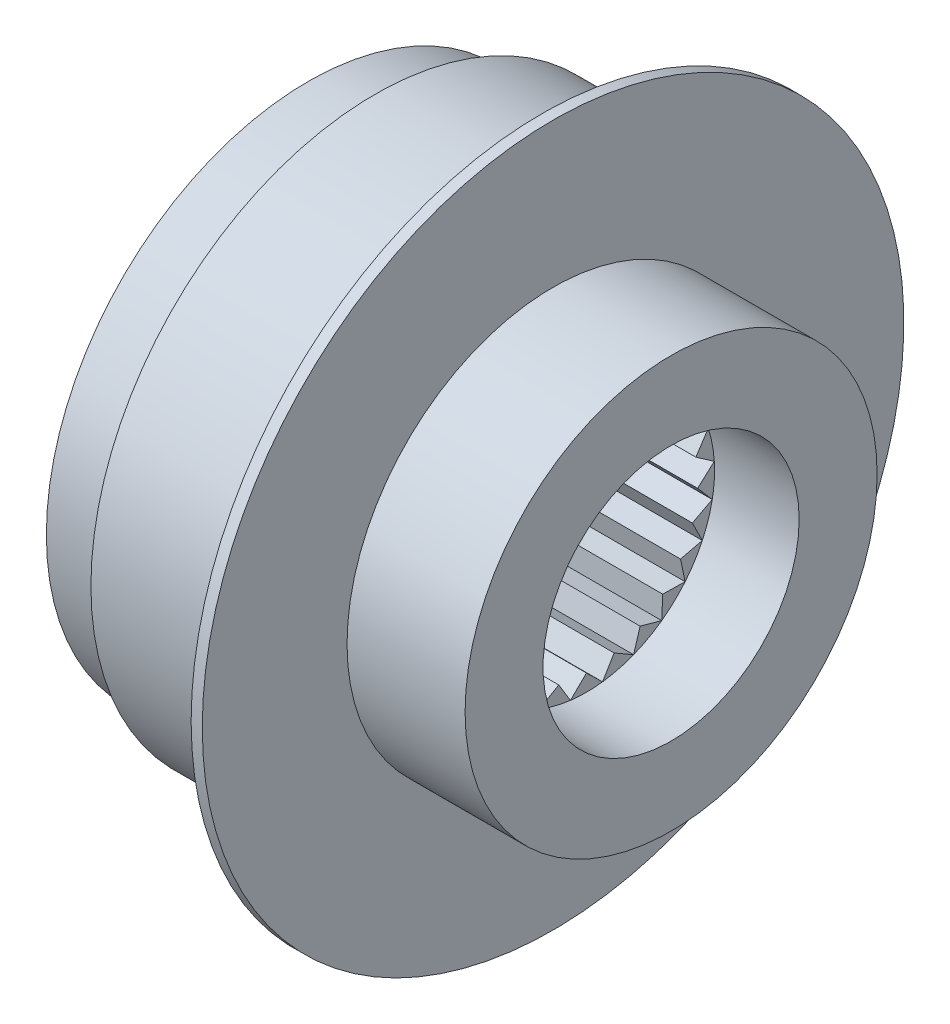
SolidWorks part; units mm, degrees
material "AISI 4130 Steel, normalized at 870C"
ref_plane "X-Y Datum" through (0, 0, 0) normal (0, 0, 1) x (1, 0, 0)
ref_plane "X-Z Datum" through (0, 0, 0) normal (0, 1, 0) x (1, 0, 0)
ref_plane "Y-Z Datum" through (0, 0, 0) normal (1, 0, 0) x (0, 0, -1)
sketch "Sketch1" plane through (0, 0, 0) normal (0, 1, 0) x (1, 0, 0)
  line L0 (-34.0129, 0) -> (34.0129, 0) construction
  line L11 (-20.701, -12.7) -> (-20.701, -29.845)
  line L12 (-20.701, -29.845) -> (-13.081, -29.845)
  line L13 (-13.081, -29.845) -> (-13.081, -32.385)
  line L14 (-13.081, -32.385) -> (5.969, -32.385)
  line L15 (5.969, -32.385) -> (5.969, -40.005)
  line L16 (5.969, -40.005) -> (7.239, -40.005)
  line L17 (7.239, -40.005) -> (7.239, -23.495)
  line L18 (7.239, -23.495) -> (20.701, -23.495)
  line L19 (20.701, -23.495) -> (20.701, -12.7)
  line L20 (20.701, -12.7) -> (-20.701, -12.7)
  point P4 (0, -12.7)
  dimension "D1" = 41.402
  dimension "D2" = 16.51
  dimension "D3" = 1.27
  dimension "D4" = 2.54
  dimension "D5" = 20.32
  dimension "D6" = 7.62
  dimension "D7" = 12.7
  dimension "D8" = 10.795
  dimension "D9" = 7.62
revolve "Revolve1" add sketch "Sketch1" angle 360 about L0
sketch "Sketch2" plane through (-20.701, 0, 0) normal (1, 0, 0) x (0, 0, -1)
  line L0 (0, 0) -> (22.225, 0) construction
  line L1 (0, 0) -> (-11.1125, -19.2474) construction
  circle A0 centre (0, 0) radius 22.225 construction
  circle A1 centre (22.225, 0) radius 3.9688
  circle A2 centre (-11.1125, -19.2474) radius 3.9687
  circle A3 centre (-11.1125, 19.2474) radius 3.9688
  dimension "D1" = 44.45
  dimension "D2" = 7.9375
  dimension "D4" = 120
  dimension "D5" = 22.225
  dimension "D3" = 3
extrude "Cut-Extrude1" cut sketch "Sketch2" along normal blind 6.35
sketch "Sketch3" plane through (20.701, 0, 0) normal (1, 0, 0) x (0, 0, -1)
  line L0 (0, 0) -> (0, -12.7) construction
  line L1 (0, 0) -> (1.5917, -12.5999) construction
  line L2 (0, 0) -> (3.1584, -12.301) construction
  line L3 (3.1584, -12.301) -> (1.8305, -14.4898)
  line L4 (1.8305, -14.4898) -> (0, -12.7)
  line L5 (-1.8305, -14.4898) -> (-3.1584, -12.301)
  line L6 (0, -12.7) -> (-1.8305, -14.4898)
  line L7 (-5.3765, -13.5794) -> (-6.1183, -11.1291)
  line L8 (-3.1584, -12.301) -> (-5.3765, -13.5794)
  line L9 (-8.5846, -11.8157) -> (-8.6937, -9.2579)
  line L10 (-6.1183, -11.1291) -> (-8.5846, -11.8157)
  line L11 (-11.2533, -9.3096) -> (-10.723, -6.805)
  line L12 (-8.6937, -9.2579) -> (-11.2533, -9.3096)
  line L13 (-13.215, -6.2185) -> (-12.0784, -3.9245)
  line L14 (-10.723, -6.805) -> (-13.215, -6.2185)
  line L15 (-14.3463, -2.7367) -> (-12.6749, -0.7974)
  line L16 (-12.0784, -3.9245) -> (-14.3463, -2.7367)
  line L17 (-14.5762, 0.9171) -> (-12.475, 2.3797)
  line L18 (-12.6749, -0.7974) -> (-14.5762, 0.9171)
  line L19 (-13.8902, 4.5132) -> (-11.4913, 5.4074)
  line L20 (-12.475, 2.3797) -> (-13.8902, 4.5132)
  line L21 (-12.3314, 7.8258) -> (-9.7855, 8.0953)
  line L22 (-11.4913, 5.4074) -> (-12.3314, 7.8258)
  line L23 (-9.9978, 10.6466) -> (-7.4649, 10.2745)
  line L24 (-9.7855, 8.0953) -> (-9.9978, 10.6466)
  line L25 (-7.036, 12.7985) -> (-4.6752, 11.8082)
  line L26 (-7.4649, 10.2745) -> (-7.036, 12.7985)
  line L27 (-3.6321, 14.1462) -> (-1.5917, 12.5999)
  line L28 (-4.6752, 11.8082) -> (-3.6321, 14.1462)
  line L29 (0, 14.605) -> (1.5917, 12.5999)
  line L30 (-1.5917, 12.5999) -> (0, 14.605)
  line L31 (3.6321, 14.1462) -> (4.6752, 11.8082)
  line L32 (1.5917, 12.5999) -> (3.6321, 14.1462)
  line L33 (7.036, 12.7985) -> (7.4649, 10.2745)
  line L34 (4.6752, 11.8082) -> (7.036, 12.7985)
  line L35 (9.9978, 10.6466) -> (9.7855, 8.0953)
  line L36 (7.4649, 10.2745) -> (9.9978, 10.6466)
  line L37 (12.3314, 7.8258) -> (11.4913, 5.4074)
  line L38 (9.7855, 8.0953) -> (12.3314, 7.8258)
  line L39 (13.8902, 4.5132) -> (12.475, 2.3797)
  line L40 (11.4913, 5.4074) -> (13.8902, 4.5132)
  line L41 (14.5762, 0.9171) -> (12.6749, -0.7974)
  line L42 (12.475, 2.3797) -> (14.5762, 0.9171)
  line L43 (14.3463, -2.7367) -> (12.0784, -3.9245)
  line L44 (12.6749, -0.7974) -> (14.3463, -2.7367)
  line L45 (13.215, -6.2185) -> (10.723, -6.805)
  line L46 (12.0784, -3.9245) -> (13.215, -6.2185)
  line L47 (11.2533, -9.3096) -> (8.6937, -9.2579)
  line L48 (10.723, -6.805) -> (11.2533, -9.3096)
  line L49 (8.5846, -11.8157) -> (6.1183, -11.1291)
  line L50 (8.6937, -9.2579) -> (8.5846, -11.8157)
  line L51 (5.3765, -13.5794) -> (3.1584, -12.301)
  line L52 (6.1183, -11.1291) -> (5.3765, -13.5794)
  circle A0 centre (0, 0) radius 12.7 construction
  circle A1 centre (0, 0) radius 14.605
  arc A2 (0, -12.7) -> (3.1584, -12.301) centre (0, 0) ccw
  arc A3 (-3.1584, -12.301) -> (0, -12.7) centre (0, 0) ccw
  arc A4 (-6.1183, -11.1291) -> (-3.1584, -12.301) centre (0, 0) ccw
  arc A5 (-8.6937, -9.2579) -> (-6.1183, -11.1291) centre (0, 0) ccw
  arc A6 (-10.723, -6.805) -> (-8.6937, -9.2579) centre (0, 0) ccw
  arc A7 (-12.0784, -3.9245) -> (-10.723, -6.805) centre (0, 0) ccw
  arc A8 (-12.6749, -0.7974) -> (-12.0784, -3.9245) centre (0, 0) ccw
  arc A9 (-12.475, 2.3797) -> (-12.6749, -0.7974) centre (0, 0) ccw
  arc A10 (-11.4913, 5.4074) -> (-12.475, 2.3797) centre (0, 0) ccw
  arc A11 (-9.7855, 8.0953) -> (-11.4913, 5.4074) centre (0, 0) ccw
  arc A12 (-7.4649, 10.2745) -> (-9.7855, 8.0953) centre (0, 0) ccw
  arc A13 (-4.6752, 11.8082) -> (-7.4649, 10.2745) centre (0, 0) ccw
  arc A14 (-1.5917, 12.5999) -> (-4.6752, 11.8082) centre (0, 0) ccw
  arc A15 (1.5917, 12.5999) -> (-1.5917, 12.5999) centre (0, 0) ccw
  arc A16 (4.6752, 11.8082) -> (1.5917, 12.5999) centre (0, 0) ccw
  arc A17 (7.4649, 10.2745) -> (4.6752, 11.8082) centre (0, 0) ccw
  arc A18 (9.7855, 8.0953) -> (7.4649, 10.2745) centre (0, 0) ccw
  arc A19 (11.4913, 5.4074) -> (9.7855, 8.0953) centre (0, 0) ccw
  arc A20 (12.475, 2.3797) -> (11.4913, 5.4074) centre (0, 0) ccw
  arc A21 (12.6749, -0.7974) -> (12.475, 2.3797) centre (0, 0) ccw
  arc A22 (12.0784, -3.9245) -> (12.6749, -0.7974) centre (0, 0) ccw
  arc A23 (10.723, -6.805) -> (12.0784, -3.9245) centre (0, 0) ccw
  arc A24 (8.6937, -9.2579) -> (10.723, -6.805) centre (0, 0) ccw
  arc A25 (6.1183, -11.1291) -> (8.6937, -9.2579) centre (0, 0) ccw
  arc A26 (3.1584, -12.301) -> (6.1183, -11.1291) centre (0, 0) ccw
  circle M5 centre (0, 0) radius 12.7
  dimension "D1" = 1.905
  dimension "D4" = 25
  dimension "D2" = 7.2
  dimension "D3" = 14.4
extrude "Cut-Extrude2" cut sketch "Sketch3" along normal blind 31.75 from surface contours L14 L13 M5 | L16 L15 M5 | L18 L17 M5 | L20 L19 M5 | L22 L21 M5 | L24 L23 M5 | L26 L25 M5 | L28 L27 M5 | L30 L29 M5 | L32 L31 M5 | L34 L33 M5 | L36 L35 M5 | L38 L37 M5 | L40 L39 M5 | L42 L41 M5 | L44 L43 M5 | L46 L45 M5 | L48 L47 M5 | L50 L49 M5 | L4 L3 M5 | L6 L5 M5 | L8 L7 M5 | L10 L9 M5 | L12 L11 M5 | L52 L51 A26 region at (20.701, -13.2081, -1.6686) region at (20.701, -13.2081, 1.6686) region at (20.701, -10.7705, -7.8252) region at (20.701, -12.3782, 4.9009) region at (20.701, -8.4861, -10.2579) region at (20.701, -10.7705, 7.8252) region at (20.701, -5.6684, -12.0461) region at (20.701, -8.4861, 10.2579) region at (20.701, -2.4946, -13.0773) region at (20.701, -5.6684, 12.0461) region at (20.701, 0.8359, -13.2868) region at (20.701, -2.4946, 13.0773) region at (20.701, 0.8359, 13.2868) region at (20.701, 4.114, -12.6615) region at (20.701, 4.114, 12.6615) region at (20.701, 7.1335, -11.2406) region at (20.701, 7.1335, 11.2406) region at (20.701, 9.7048, -9.1134) region at (20.701, 9.7048, 9.1134) region at (20.701, 11.6664, -6.4136) region at (20.701, 11.6664, 6.4136) region at (20.701, 12.8948, -3.3108) region at (20.701, 12.8948, 3.3108) region at (20.701, 13.3131, 0) starting at face at (-20.701, 0, -26.1937)
extrude "Cut-Extrude3" cut sketch "Sketch3<4>" against normal up to surface (9.652 mm away) contours L50 A1 L47 | M5 | L50 L49 M5 | L52 A1 L49 | L52 L51 M5 | L3 A1 L51 | L4 L3 M5 | L6 A1 L4 | L12 A1 L9 | L14 A1 L11 | L14 L13 M5 | L16 L15 M5 | L18 A1 L15 | L20 A1 L17 | L20 L19 M5 | L22 A1 L19 | L22 L21 M5 | L28 L27 M5 | L30 L29 M5 | L32 L31 M5 | L34 L33 M5 | L36 A1 L33 | L38 A1 L35 | L40 A1 L37 | L40 L39 M5 | L42 A1 L39 | L44 A1 L41 | L44 L43 M5 | L46 A1 L43 | L46 L45 M5 | L48 A1 L45 | L48 L47 M5 | L6 L5 M5 | L8 A1 L5 | L8 L7 M5 | L10 A1 L7 | L10 L9 M5 | L12 L11 M5 | L16 A1 L13 | L18 L17 M5 | L24 A1 L21 | L24 L23 M5 | L26 A1 L23 | L28 A1 L25 | L30 A1 L27 | L32 A1 L29 | L34 A1 L31 | L36 L35 M5 | L42 L41 M5 | L38 L37 M5 | L26 L25 M5 | A1 | A25 L50 L49 | L23 A12 L24 | L28 L27 A14 | L30 L29 A15 | L31 A16 L32 | L36 L35 A18 | L39 A20 L40 | L41 A21 L42 | L43 A22 L44 region at (20.701, -13.506, -3.4677) region at (20.701, -12.3782, -4.9009) region at (20.701, -13.2081, -1.6686) region at (20.701, 0, 0) region at (20.701, -13.944, 0) region at (20.701, -12.2193, -6.7176) region at (20.701, -13.2081, 1.6686) region at (20.701, -10.7705, -7.8252) region at (20.701, -13.506, 3.4677) region at (20.701, -10.1648, -9.5454) region at (20.701, -12.3782, 4.9009) region at (20.701, -8.4861, -10.2579) region at (20.701, -12.2193, 6.7176) region at (20.701, -7.4716, -11.7733) region at (20.701, -10.7705, 7.8252) region at (20.701, -5.6684, -12.0461) region at (20.701, -10.1648, 9.5454) region at (20.701, -4.3089, -13.2616) region at (20.701, -8.4861, 10.2579) region at (20.701, -2.4946, -13.0773) region at (20.701, -7.4716, 11.7733) region at (20.701, -0.8756, -13.9165) region at (20.701, -5.6684, 12.0461) region at (20.701, 0.8359, -13.2868) region at (20.701, -4.3089, 13.2616) region at (20.701, -2.4946, 13.0773) region at (20.701, 2.6129, -13.6971) region at (20.701, -0.8756, 13.9165) region at (20.701, 0.8359, 13.2868) region at (20.701, 4.114, -12.6615) region at (20.701, 5.9371, -12.6169) region at (20.701, 2.6129, 13.6971) region at (20.701, 4.114, 12.6615) region at (20.701, 7.1335, -11.2406) region at (20.701, 8.8883, -10.7441) region at (20.701, 5.9371, 12.6169) region at (20.701, 7.1335, 11.2406) region at (20.701, 9.7048, -9.1134) region at (20.701, 11.281, -8.1961) region at (20.701, 8.8883, 10.7441) region at (20.701, 9.7048, 9.1134) region at (20.701, 11.6664, -6.4136) region at (20.701, 12.9648, -5.1331) region at (20.701, 11.281, 8.1961) region at (20.701, 11.6664, 6.4136) region at (20.701, 12.8948, -3.3108) region at (20.701, 13.8341, -1.7477) region at (20.701, 12.9648, 5.1331) region at (20.701, 12.8948, 3.3108) region at (20.701, 13.3131, 0) region at (20.701, 13.8341, 1.7477) up to face at (11.049, 0.8352, -13.2754)
sketch "Sketch3<4>" plane through (20.701, 0, 0) normal (1, 0, 0) x (0, 0, -1) same geometry as "Sketch3"
